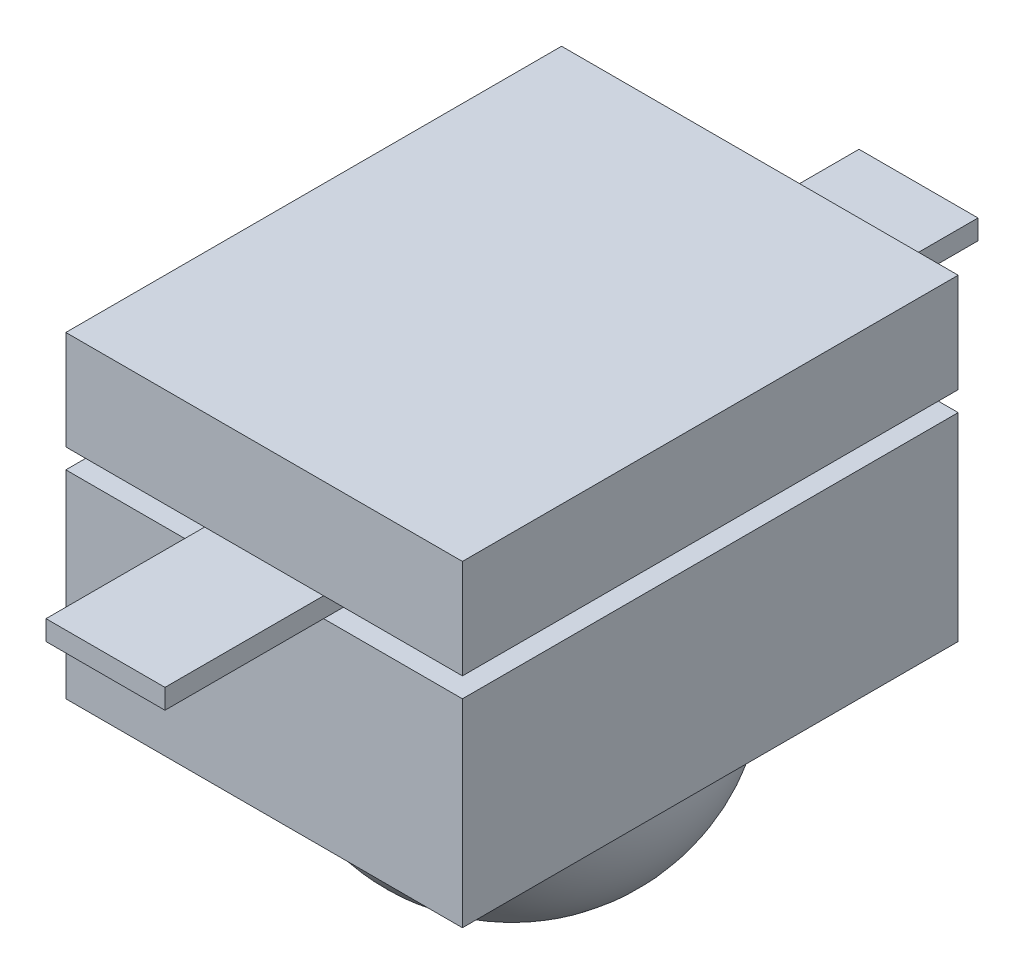
SolidWorks part; units mm, degrees
ref_plane "Piano frontale" through (0, 0, 0) normal (0, 0, 1) x (1, 0, 0)
ref_plane "Piano superiore" through (0, 0, 0) normal (0, 1, 0) x (1, 0, 0)
ref_plane "Piano destro" through (0, 0, 0) normal (1, 0, 0) x (0, 0, -1)
sketch "Schizzo1" plane through (0, 0, 0) normal (0, 1, 0) x (1, 0, 0)
  line L1 (-10.5604, -7.2481) -> (-8.5604, -7.2481)
  line L2 (-10.5604, -7.2481) -> (-10.5604, -9.7481)
  line L3 (-10.5604, -9.7481) -> (-8.5604, -9.7481)
  line L4 (-8.5604, -7.2481) -> (-8.5604, -9.7481)
  dimension "D1" = 2.5
  dimension "D2" = 2
extrude "Estrusione-Estrusione1" add sketch "Schizzo1" along normal blind 1
sketch "Schizzo2" plane through (0, 0, 0) normal (0, -1, 0) x (1, 0, 0)
  line L0 (-8.5604, 9.7481) -> (-8.5604, 7.2481) construction
  line L1 (-8.5604, 7.2481) -> (-10.5604, 7.2481) construction
  circle A0 centre (-9.5604, 8.4981) radius 0.9
  dimension "D1" = 1
  dimension "D2" = 1.25
extrude "Estrusione-Estrusione2" add sketch "Schizzo2" along normal blind 0.9
fillet "Raccordo1" radius 0.9 1 edges at (-9.5604, -0.9, 7.5981)
sketch "Schizzo4" plane through (0, 1, 0) normal (0, 1, 0) x (1, 0, 0)
  line L0 (-10.3604, -8.8481) -> (-9.2104, -8.8481)
  line L1 (-9.2104, -8.12) -> (-8.7604, -8.12)
  line L2 (-8.7604, -8.12) -> (-8.7604, -7.4481)
  line L3 (-8.7604, -7.4481) -> (-10.3604, -7.4481)
  line L4 (-10.3604, -7.4481) -> (-10.3604, -8.8481)
  line L5 (-9.2104, -8.8481) -> (-9.2104, -8.12)
  line L6 (-8.5604, -7.2481) -> (-10.5604, -7.2481) construction
  line L7 (-8.5604, -9.7481) -> (-8.5604, -7.2481) construction
  line L9 (-10.3604, -8.9481) -> (-9.1104, -8.9481)
  line L10 (-9.1104, -8.9481) -> (-9.1104, -8.22)
  line L11 (-9.1104, -8.22) -> (-8.7604, -8.22)
  line L12 (-8.7604, -8.22) -> (-8.7604, -9.5481)
  line L13 (-8.7604, -9.5481) -> (-10.3604, -9.5481)
  line L14 (-10.3604, -9.5481) -> (-10.3604, -8.9481)
  line L15 (-10.5604, -9.7481) -> (-8.5604, -9.7481) construction
  line L16 (-10.5604, -7.2481) -> (-10.5604, -9.7481) construction
  line L18 (-9.8604, -9.5481) -> (-9.2604, -9.5481)
  line L19 (-9.8604, -9.5481) -> (-9.8604, -10.5481)
  line L20 (-9.8604, -10.5481) -> (-9.2604, -10.5481)
  line L21 (-9.2604, -9.5481) -> (-9.2604, -10.5481)
  line L22 (-9.8604, -7.4481) -> (-9.2604, -7.4481)
  line L23 (-9.8604, -7.4481) -> (-9.8604, -6.4481)
  line L24 (-9.8604, -6.4481) -> (-9.2604, -6.4481)
  line L25 (-9.2604, -7.4481) -> (-9.2604, -6.4481)
  dimension "D1" = 1.6
  dimension "D2" = 0.2
  dimension "D3" = 0.2
  dimension "D4" = 1.4
  dimension "D5" = 0.1
  dimension "D6" = 1.15
  dimension "D7" = 0.1
  dimension "D8" = 0.1
  dimension "D9" = 0.2
  dimension "D10" = 0.2
  dimension "D11" = 0.2
  dimension "D12" = 0.6
  dimension "D13" = 0.5
  dimension "D14" = 1
  dimension "D15" = 1
  dimension "D16" = 0.6
  dimension "D17" = 0.5
extrude "Estrusione-Estrusione3" add sketch "Schizzo4" along normal blind 0.1 contours L23 L24 L25 L22 | L3 L4 L0 L5 L1 L2 | L9 L10 L11 L12 L13 L14 | L19 L20 L21 L18
sketch "Schizzo6" plane through (0, 1.1, 0) normal (0, 1, 0) x (1, 0, 0)
  line L1 (-9.8604, -7.2481) -> (-10.5604, -7.2481) construction
  line L2 (-8.5604, -7.2481) -> (-8.5604, -9.7481)
  line L3 (-10.5604, -7.2481) -> (-8.5604, -7.2481)
  line L7 (-8.5604, -9.7481) -> (-10.5604, -9.7481)
  line L8 (-10.5604, -9.7481) -> (-10.5604, -7.2481)
  dimension "D1" = 0
  dimension "D2" = 2
  dimension "D3" = 0
  dimension "D4" = 0
extrude "Estrusione-Estrusione5" add sketch "Schizzo6" along normal blind 0.5
